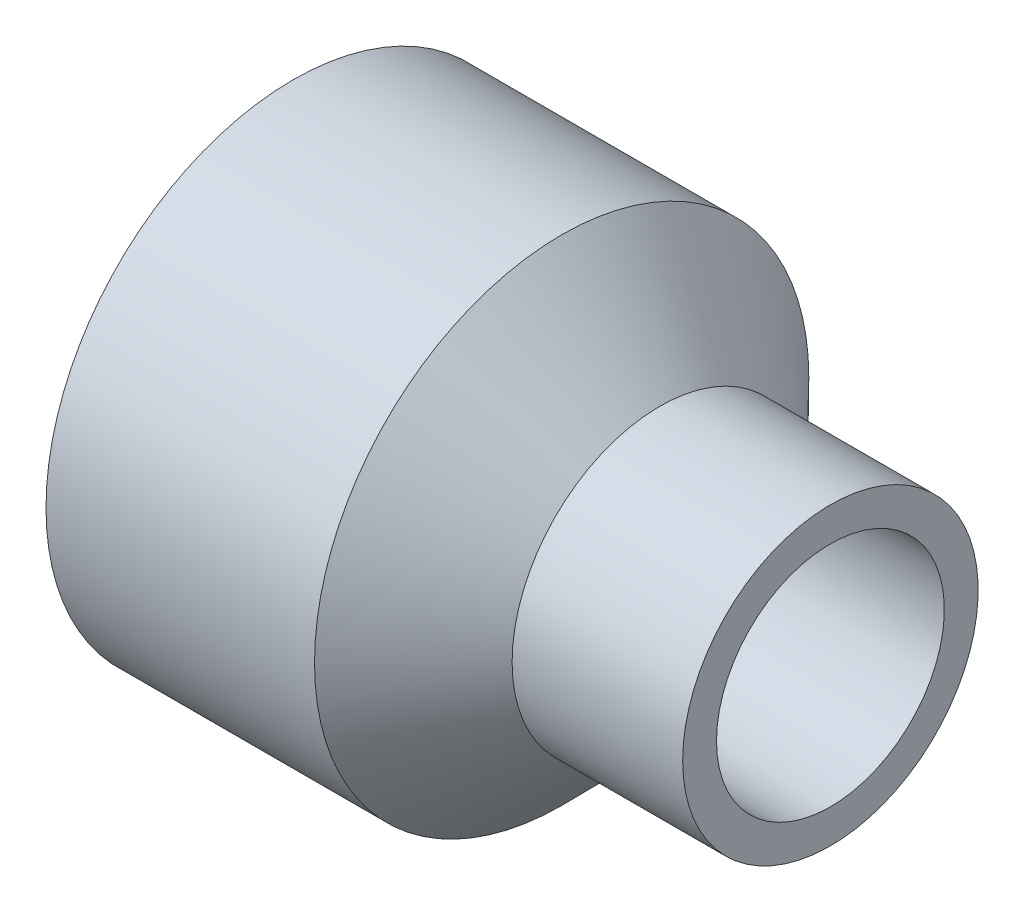
SolidWorks part; units mm, degrees
ref_plane "Front Plane" through (0, 0, 0) normal (0, 0, 1) x (1, 0, 0)
ref_plane "Top Plane" through (0, 0, 0) normal (0, 1, 0) x (1, 0, 0)
ref_plane "Right Plane" through (0, 0, 0) normal (1, 0, 0) x (0, 0, -1)
sketch "Sketch0" plane through (0, 0, 0) normal (0, 0, 1) x (1, 0, 0)
  line L0 (-39.6875, 0) -> (11.1125, 0) construction
  line L2 (-2.3812, 0) -> (11.1125, 0) construction
  line L3 (-39.6875, 0) -> (39.6875, 0) construction
  line L4 (-39.6875, 36.5125) -> (-39.6875, -36.5125) construction
  line L5 (-2.3812, 30.0863) -> (-39.6875, 30.3149) construction
  line L6 (-2.3812, 30.0863) -> (-2.3812, -30.0863) construction
  line L7 (-2.3812, -30.0863) -> (-39.6875, -30.3149) construction
  line L8 (-39.6875, 30.3149) -> (-39.6875, -30.3149) construction
  line L9 (39.6875, 16.8275) -> (39.6875, -16.8275) construction
  line L10 (39.6875, 21.8281) -> (39.6875, -21.8281) construction
  line L11 (11.1125, 12.1539) -> (11.1125, -12.1539) construction
  line L12 (11.1125, 16.637) -> (11.1125, -16.637) construction
  line L13 (11.1125, -16.637) -> (39.6875, -16.8275) construction
  line L14 (-2.3812, 24.6253) -> (-2.3812, -24.6253) construction
  line L15 (11.1125, 16.637) -> (39.6875, 16.8275) construction
  dimension "N" = 13.4937
  dimension "M" = 73.025
  dimension "OD A" = 60.6298
  dimension "OD B" = 60.1726
  dimension "ID" = 49.2506
  dimension "L" = 79.375
  dimension "ID2" = 24.3078
  dimension "OD B2" = 33.274
  dimension "OD A2" = 33.655
  dimension "M2" = 43.6562
  dimension "C" = 37.3062
  dimension "C2" = 28.575
sketch "Sketch1" plane through (0, 0, 0) normal (0, 0, 1) x (1, 0, 0)
  line L0 (-39.6875, 0) -> (11.1125, 0) construction
  line L1 (-39.6875, 0) -> (11.1125, 0) construction
  line L2 (-2.3812, -30.0863) -> (13.1185, -14.3954) construction
  line L3 (0, -36.4946) -> (-4.4091, -32.1392) construction
  line L4 (-39.6875, -36.5125) -> (-39.6875, -30.3149)
  line L5 (-39.6875, -30.3149) -> (-2.3812, -30.0863)
  line L6 (11.1125, -14.3954) -> (8.8433, -14.3954) construction
  line L7 (8.8433, -14.3954) -> (11.1125, -16.637) construction
  line L8 (-0.0177, -36.5125) -> (14.4878, -21.8281)
  line L9 (-0.0177, -36.5125) -> (-39.6875, -36.5125)
  line L10 (0, 0) -> (0, -36.4946) construction
  line L11 (8.8433, -14.3954) -> (13.1185, -14.3954) construction
  line L12 (11.1125, -16.637) -> (39.6875, -16.8275)
  line L13 (39.6875, -16.8275) -> (39.6875, -21.8281)
  line L14 (39.6875, -21.8281) -> (14.4878, -21.8281)
  line L15 (11.1125, -12.1539) -> (11.1125, -16.637) construction
  line L16 (11.1125, -16.637) -> (8.8433, -14.3954)
  line L17 (8.8433, -14.3954) -> (-2.3812, -30.0863)
  dimension "D1" = 45
revolve "Revolve1" add sketch "Sketch1" angle 360 about L1
other "CPoint1" parameters "Diameter"=50.8, "StubLength"=76.2
ref_axis "Axis1" through (-12.3812, 0, 0) along (1, 0, 0)
other "CPoint2" parameters "Diameter"=25.4, "StubLength"=76.2
ref_axis "Axis2" through (21.1125, 0, 0) along (-1, 0, 0)
other "RPoint1"
